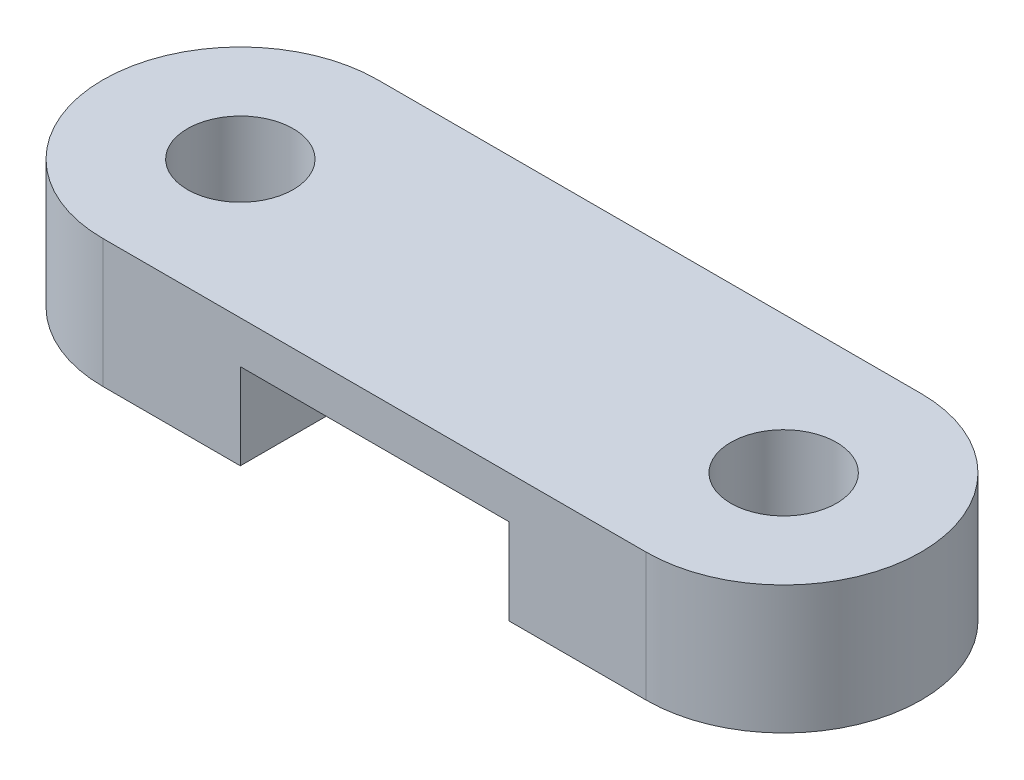
SolidWorks part; units mm, degrees
ref_plane "Front Plane" through (0, 0, 0) normal (0, 0, 1) x (1, 0, 0)
ref_plane "Top Plane" through (0, 0, 0) normal (0, 1, 0) x (1, 0, 0)
ref_plane "Right Plane" through (0, 0, 0) normal (1, 0, 0) x (0, 0, -1)
sketch "Sketch2" plane through (0, 0, 0) normal (0, 1, 0) x (1, 0, 0)
  line L0 (-6.425, 0) -> (6.425, 0) construction
  line L1 (-6.425, 3.25) -> (6.425, 3.25)
  line L2 (-6.425, -3.25) -> (6.425, -3.25)
  line L4 (-3.175, -3.25) -> (3.175, -3.25) construction
  line L5 (-3.175, -3.25) -> (-3.175, 3.25)
  line L6 (-3.175, 3.25) -> (3.175, 3.25) construction
  line L7 (3.175, -3.25) -> (3.175, 3.25)
  arc A0 (-6.425, 3.25) -> (-6.425, -3.25) centre (-6.425, 0) ccw
  arc A1 (6.425, -3.25) -> (6.425, 3.25) centre (6.425, 0) ccw
  circle A2 centre (6.425, 0) radius 1.25
  circle A3 centre (-6.425, 0) radius 1.25
  point P2 (0, 0)
  point P12 (2.7571, -3.25)
  point P13 (-2.1852, 3.25)
  dimension "D1" = 2.5
  dimension "D2" = 2
  dimension "D3" = 6.35
extrude "Boss-Extrude1" add sketch "Sketch2" along normal blind 1 contours L1 A0 L2 L5 A3 | L2 L7 L1 L5 | L2 A1 L1 L7 A2 region at (-4.8, 0, -3.1581) region at (0, 0, 0) region at (4.8, 0, -3.1581)
extrude "Boss-Extrude2" add sketch "Sketch2<3>" against normal blind 2.032 contours L1 A0 L2 L5 A3 | L2 A1 L1 L7 A2 region at (-4.8, 0, -3.1581) region at (4.8, 0, -3.1581)
sketch "Sketch2<3>" plane through (0, 0, 0) normal (0, 1, 0) x (1, 0, 0) same geometry as "Sketch2"
